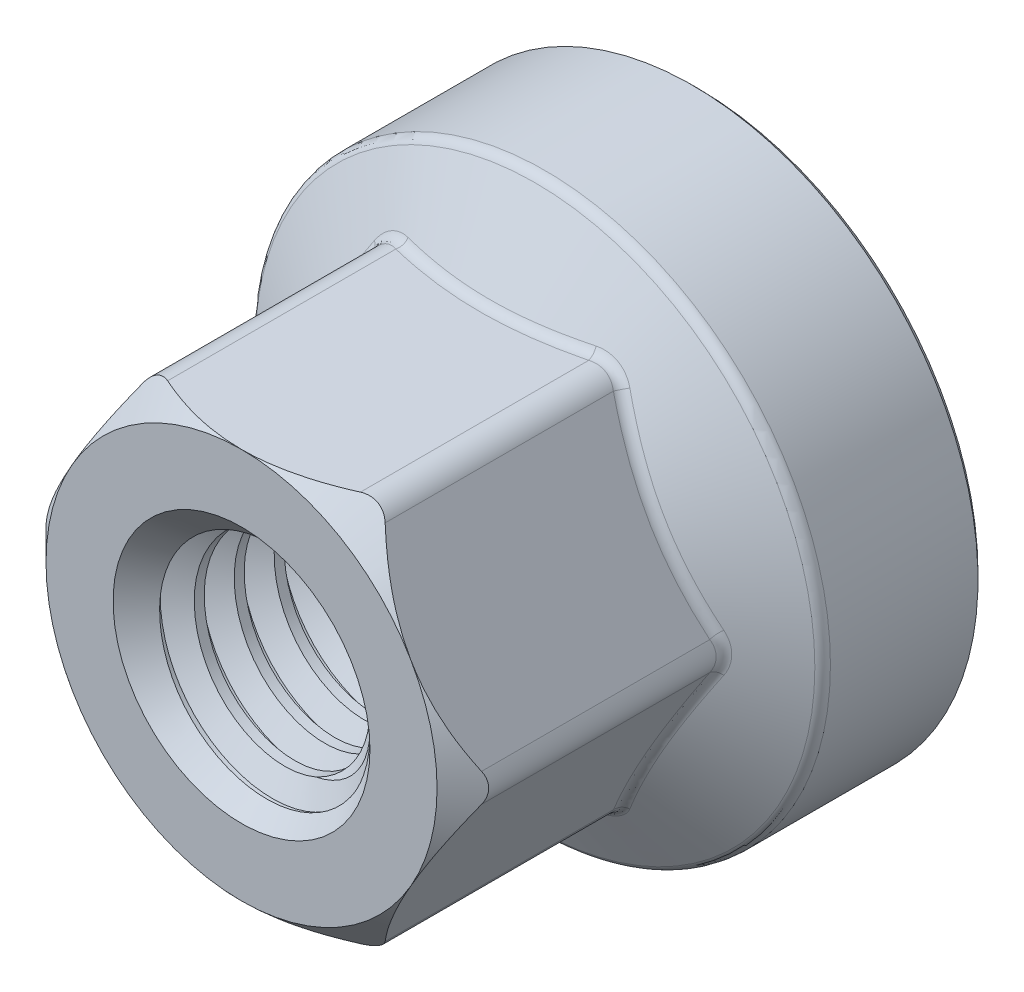
SolidWorks part; units mm, degrees
material "316 Stainless Steel"
ref_plane "Front Plane" through (0, 0, 0) normal (0, 0, 1) x (1, 0, 0)
ref_plane "Top Plane" through (0, 0, 0) normal (0, 1, 0) x (1, 0, 0)
ref_plane "Right Plane" through (0, 0, 0) normal (1, 0, 0) x (0, 0, -1)
ref_axis "CL" through (0, 0, -7.5614) along (0, 0, 1)
sketch "Sketch3" plane through (0, 0, 0) normal (1, 0, 0) x (0, 0, -1)
  line L0 (0, 0) -> (0, 5)
  line L1 (0, 5) -> (-2.8, 5)
  line L2 (-2.8, 5) -> (-4.4755, 2.098)
  line L3 (-4.4755, 2.098) -> (-4.4755, 0)
  line L4 (-4.4755, 0) -> (0, 0)
  line L5 (-3.7093, 3.425) -> (-8, 3.425) construction
  line L6 (-8, 3.425) -> (-8, 0) construction
  line L7 (-8, 0) -> (-4.4755, 0) construction
  line L8 (0, 0) -> (1.8049, 0) construction
  point P9 (0, 0)
  dimension "D1" = 10
  dimension "D2" = 2.8
  dimension "D3" = 60
  dimension "D4" = 8
  dimension "D5" = 6.85
revolve "Revolve2" add sketch "Sketch3" angle 360 about axis through (0, 0, -7.5614) along (0, 0, 1)
ref_plane "Plane2" through (0, 0, 8) normal (0, 0, 1) x (1, 0, 0)
sketch "Sketch5" plane through (0, 0, 8) normal (0, 0, 1) x (1, 0, 0)
  line L1 (1.9774, -3.425) -> (3.9548, 0)
  line L2 (3.9548, 0) -> (1.9774, 3.425)
  line L3 (1.9774, 3.425) -> (-1.9774, 3.425)
  line L4 (-1.9774, 3.425) -> (-3.9548, 0)
  line L5 (-3.9548, 0) -> (-1.9774, -3.425)
  line L6 (-1.9774, -3.425) -> (1.9774, -3.425)
  circle A0 centre (0, 0) radius 3.425 construction
extrude "Boss-Extrude1" add sketch "Sketch5" against normal up to next
sketch "Sketch6" plane through (0, 0, 0) normal (1, 0, 0) x (0, 0, -1)
  line L0 (-8, 3.425) -> (-8, 4.425)
  line L1 (-8, 4.425) -> (-7, 4.425)
  line L2 (-7, 4.425) -> (-8, 3.425)
  dimension "D1" = 45
  dimension "D2" = 1
revolve "Cut-Revolve1" cut sketch "Sketch6" angle 360 about axis through (0, 0, -7.5614) along (0, 0, 1)
fillet "Fillet4" radius 0.1 1 edges at (-5, 0, 0) profile chamfer
sketch "Sketch9" plane through (0, 0, 0) normal (0, 0, -1) x (-1, 0, 0)
  point P0 (0, 0)
hole_wizard "M4x0.7 Tapped Hole1" positions "Sketch9" profile "Sketch10" tap size "M4x0.7" standard "ANSI Metric" end condition through all
sketch "Sketch10" plane through (0, 0, 0) normal (1, 0, 0) x (0, 1, 0)
  line L0 (0, 0) -> (0, 8)
  line L1 (0, 8) -> (1.65, 8)
  line L2 (1.65, 8) -> (1.65, 0)
  line L5 (1.65, 0) -> (0, 0)
  line L11 (0, -6.35) -> (0, 107.95) construction
  dimension "Thru Tap Drill Dia." = 3.3
  dimension "Thru Tap Drill Depth" = 8
chamfer "Chamfer3" distance 0.6 angle 45 1 edges at (-1.65, 0, 8)
chamfer "Chamfer4" distance 0.4 angle 45 1 edges at (-1.65, 0, 0)
thread "Thread2" pitch 0.7 method cut profile "Thread Profile2" start angle 0, offset 1, length 0, pitch 0.7, diameter 3.3
ref_plane "Plane3" through (-1.65, 0, 8.4) normal (0, -1, 0) x (-1, 0, 0)
sketch "Thread Profile2" plane through (-1.65, 0, 8.4) normal (0, -1, 0) x (-1, 0, 0)
  line L0 (0, 0) -> (0, 0.7) construction
  line L1 (0, 0) -> (0.3789, 0.2187)
  line L2 (0.3789, 0.2187) -> (0.3789, 0.3062)
  line L3 (0.3789, 0.3062) -> (0, 0.525)
  line L4 (0.3789, 0.2625) -> (0, 0.2625) construction
  line L11 (0, 0) -> (0, 0.525)
  point P2 (0, 0)
  dimension "Pitch" = 0.7
  dimension "Profile_Angle" = 60
  dimension "Profile_Land" = 0.0875
  dimension "Profile_Height" = 0.3789
fillet "Fillet5" radius 0.5 6 edges at (-1.9774, -3.425, 5.4368) (-3.9548, 0, 5.4368) (1.9774, -3.425, 5.4368) (3.9548, 0, 5.4368) (-1.9774, 3.425, 5.4368) (1.9774, 3.425, 5.4368)
fillet "Fillet6" radius 0.2 13 edges at (-5, 0, 2.8) (1.9776, 3.3331, 3.4491) (-0.1048, 3.425, 3.7084) (-1.8977, 3.3792, 3.4491) (-2.8959, 1.8342, 3.7077) (-3.8754, 0.0461, 3.4491) (-3.0364, -1.5908, 3.7077) (-1.9776, -3.3331, 3.4491) (0.1048, -3.425, 3.7084) (1.8977, -3.3792, 3.4491) (2.8959, -1.8342, 3.7077) (3.8754, -0.0461, 3.4491) (3.0364, 1.5908, 3.7077)
